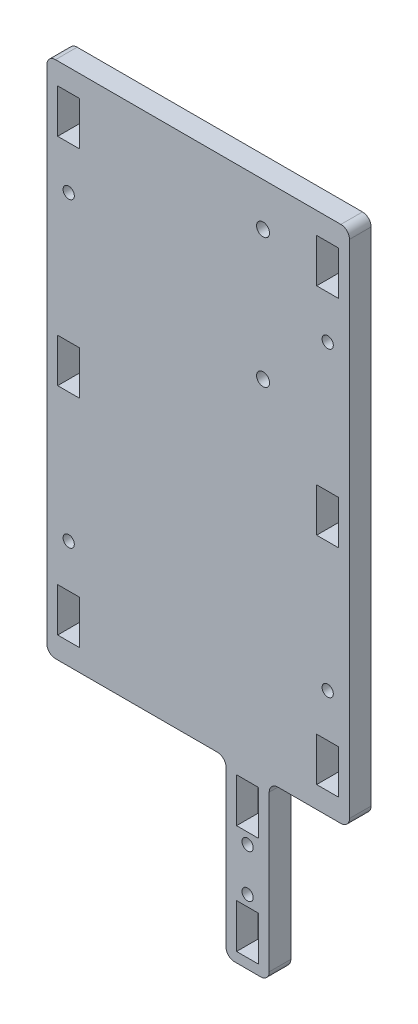
SolidWorks part; units mm, degrees
ref_plane "Front Plane" through (0, 0, 0) normal (0, 0, 1) x (1, 0, 0)
ref_plane "Top Plane" through (0, 0, 0) normal (0, 1, 0) x (1, 0, 0)
ref_plane "Right Plane" through (0, 0, 0) normal (1, 0, 0) x (0, 0, -1)
sketch "Sketch1" plane through (0, 0, 0) normal (0, 0, 1) x (1, 0, 0)
  line L0 (58.9635, -50.8) -> (58.9635, 0) construction
  line L1 (0, 0) -> (88.9, 0)
  line L2 (0, 0) -> (0, 152.4)
  line L3 (0, 152.4) -> (88.9, 152.4)
  line L4 (88.9, 0) -> (88.9, 152.4)
  line L5 (52.6135, 0) -> (65.3135, 0)
  line L6 (52.6135, 0) -> (52.6135, -50.8)
  line L7 (52.6135, -50.8) -> (65.3135, -50.8)
  line L8 (65.3135, 0) -> (65.3135, -50.8)
  line L9 (52.6135, -25.4) -> (65.3135, -25.4) construction
  line L10 (55.725, -34.925) -> (62.202, -34.925)
  line L11 (55.725, -34.925) -> (55.725, -47.879)
  line L12 (55.725, -47.879) -> (62.202, -47.879)
  line L13 (62.202, -34.925) -> (62.202, -47.879)
  line L14 (55.725, -34.925) -> (62.202, -47.879) construction
  line L15 (55.725, -47.879) -> (62.202, -34.925) construction
  line L16 (55.725, -2.921) -> (62.202, -15.875) construction
  line L17 (55.725, -15.875) -> (62.202, -2.921) construction
  line L18 (62.202, -15.875) -> (62.202, -2.921)
  line L19 (55.725, -2.921) -> (62.202, -2.921)
  line L20 (55.725, -15.875) -> (55.725, -2.921)
  line L21 (55.725, -15.875) -> (62.202, -15.875)
  point P11 (58.9635, -41.402)
  point P22 (58.9635, -9.398)
  dimension "D1" = 88.9
  dimension "D2" = 152.4
  dimension "D3" = 50.8
  dimension "D4" = 12.7
  dimension "D5" = 6.477
  dimension "D6" = 19.05
  dimension "D7" = 12.954
  dimension "D8" = 33.175
extrude "Boss-Extrude1" add sketch "Sketch1" along normal blind 6.35 contours L1 L4 L3 L2 | L8 L1 L6 L7 L21 L20 L19 L18 L10 L13 L12 L11 region at (44.45, 76.2, 0) region at (58.9635, -25.4, 0)
sketch "Sketch3" plane through (0, 0, 6.35) normal (0, 0, 1) x (1, 0, 0)
  line L0 (44.45, 152.4) -> (44.45, 0) construction
  line L1 (0, 76.2) -> (88.9, 76.2) construction
  line L2 (6.4135, 19.177) -> (6.4135, 133.223) construction
  line L3 (3.175, 146.05) -> (9.652, 146.05)
  line L4 (3.175, 146.05) -> (3.175, 133.223)
  line L5 (3.175, 133.223) -> (9.652, 133.223)
  line L6 (9.652, 146.05) -> (9.652, 133.223)
  line L7 (3.175, 19.177) -> (9.652, 19.177)
  line L8 (0, 0) -> (52.6135, 0)
  line L9 (52.6135, 0) -> (52.6135, -50.8)
  line L10 (52.6135, -50.8) -> (65.3135, -50.8)
  line L11 (65.3135, -50.8) -> (65.3135, 0)
  line L12 (65.3135, 0) -> (88.9, 0)
  line L13 (88.9, 0) -> (88.9, 152.4)
  line L14 (88.9, 152.4) -> (0, 152.4)
  line L15 (0, 152.4) -> (0, 0)
  line L16 (0, 0) -> (52.6135, 0)
  line L17 (52.6135, 0) -> (52.6135, -50.8)
  line L18 (52.6135, -50.8) -> (65.3135, -50.8)
  line L19 (65.3135, -50.8) -> (65.3135, 0)
  line L20 (65.3135, 0) -> (88.9, 0)
  line L21 (88.9, 0) -> (88.9, 152.4)
  line L22 (88.9, 152.4) -> (0, 152.4)
  line L23 (0, 152.4) -> (0, 0)
  line L24 (3.175, 19.177) -> (3.175, 6.35)
  line L25 (3.175, 6.35) -> (9.652, 6.35)
  line L26 (9.652, 19.177) -> (9.652, 6.35)
  line L27 (3.175, 82.6135) -> (9.652, 82.6135)
  line L28 (3.175, 82.6135) -> (3.175, 69.7865)
  line L29 (3.175, 69.7865) -> (9.652, 69.7865)
  line L30 (9.652, 82.6135) -> (9.652, 69.7865)
  line L31 (3.175, 82.6135) -> (9.652, 69.7865) construction
  line L32 (3.175, 69.7865) -> (9.652, 82.6135) construction
  line L33 (85.725, 69.7865) -> (79.248, 82.6135) construction
  line L34 (85.725, 82.6135) -> (79.248, 69.7865) construction
  line L35 (82.4865, 19.177) -> (82.4865, 133.223) construction
  line L36 (79.248, 82.6135) -> (79.248, 69.7865)
  line L37 (85.725, 69.7865) -> (79.248, 69.7865)
  line L38 (85.725, 82.6135) -> (85.725, 69.7865)
  line L39 (85.725, 82.6135) -> (79.248, 82.6135)
  line L40 (79.248, 19.177) -> (79.248, 6.35)
  line L41 (85.725, 6.35) -> (79.248, 6.35)
  line L42 (85.725, 19.177) -> (85.725, 6.35)
  line L43 (85.725, 19.177) -> (79.248, 19.177)
  line L44 (79.248, 146.05) -> (79.248, 133.223)
  line L45 (85.725, 133.223) -> (79.248, 133.223)
  line L46 (85.725, 146.05) -> (85.725, 133.223)
  line L47 (85.725, 146.05) -> (79.248, 146.05)
  circle A0 centre (6.4135, 120.523) radius 1.651
  circle A1 centre (6.4135, 31.877) radius 1.651
  circle A2 centre (82.4865, 31.877) radius 1.651
  circle A3 centre (82.4865, 120.523) radius 1.651
  point P20 (6.4135, 76.2)
  point P49 (82.4865, 76.2)
  dimension "D7" = 3.302
  dimension "D2" = 12.827
  dimension "D3" = 6.477
  dimension "D4" = 6.35
  dimension "D5" = 6.35
  dimension "D6" = 3.175
  dimension "D8" = 12.7
  dimension "D1" = 0
extrude "Cut-Extrude3" cut sketch "Sketch3" against normal blind 6.35 contours L6 L3 L4 L5 | L26 L7 L24 L25 | L46 L47 L44 L45 | A0 | L27 L30 L29 L28 | A1 | L40 L41 L42 L43 | A2 | A3 | L36 L37 L38 L39 region at (6.4135, 139.6365, 6.35) region at (6.4135, 12.7635, 6.35) region at (82.4865, 139.6365, 6.35)
sketch "Sketch4" plane through (0, 0, 6.35) normal (0, 0, 1) x (1, 0, 0)
  line L0 (58.9635, -15.875) -> (58.9635, -34.925) construction
  line L1 (55.725, -15.875) -> (62.202, -15.875) construction
  line L2 (55.725, -34.925) -> (62.202, -34.925) construction
  line L3 (52.6135, -25.4) -> (65.3135, -25.4) construction
  line L4 (52.6135, 0) -> (52.6135, -50.8) construction
  line L5 (65.3135, 0) -> (65.3135, -50.8) construction
  circle A0 centre (58.9635, -19.05) radius 1.651
  circle A1 centre (58.9635, -31.75) radius 1.651
  dimension "D1" = 3.302
  dimension "D2" = 12.7
extrude "Cut-Extrude4" cut sketch "Sketch4" against normal blind 6.35
fillet "Fillet1" radius 2.54 8 edges at (88.9, 152.4, 3.175) (88.9, 0, 3.175) (65.3135, 0, 3.175) (65.3135, -50.8, 3.175) (52.6135, -50.8, 3.175) (52.6135, 0, 3.175) (0, 0, 3.175) (0, 152.4, 3.175)
sketch "Sketch5" plane through (0, 0, 6.35) normal (0, 0, 1) x (1, 0, 0)
  line L0 (63.5, 152.4) -> (63.5, 0) construction
  line L1 (2.54, 152.4) -> (86.36, 152.4) construction
  line L2 (67.8535, 0) -> (86.36, 0) construction
  line L3 (88.9, 2.54) -> (88.9, 149.86) construction
  circle A0 centre (63.5, 139.7) radius 1.905
  circle A1 centre (63.5, 101.6) radius 1.905
  dimension "D2" = 3.81
  dimension "D1" = 25.4
  dimension "D3" = 38.1
  dimension "D4" = 12.7
extrude "Cut-Extrude5" cut sketch "Sketch5" against normal blind 6.35
